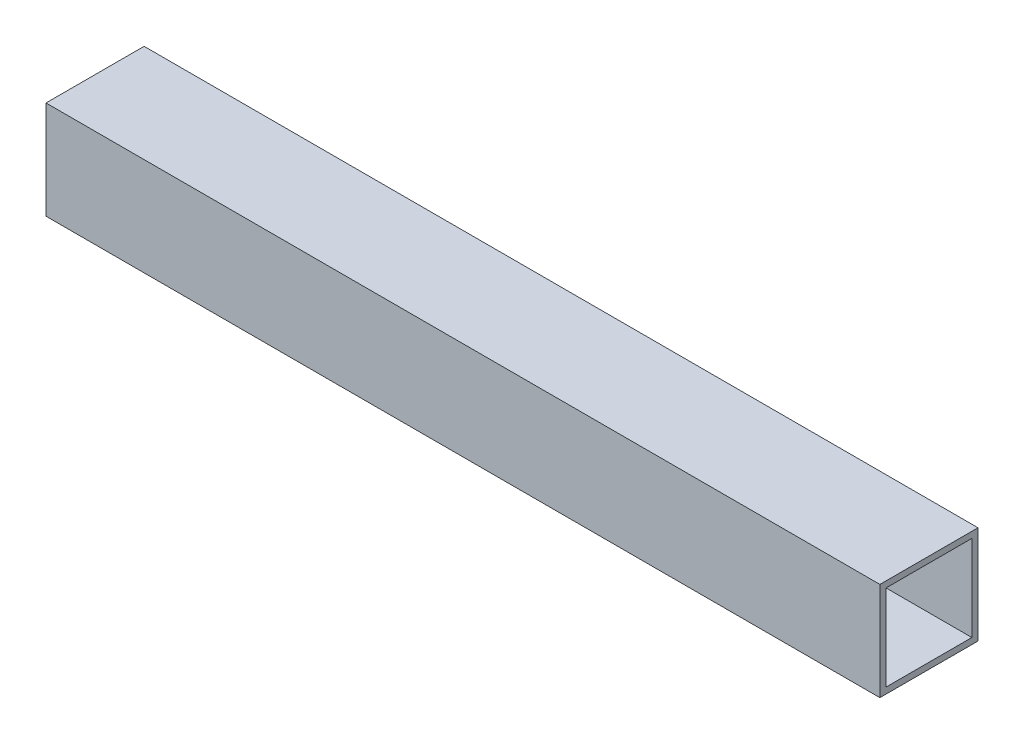
SolidWorks part; units mm, degrees
ref_plane "Front" through (0, 0, 0) normal (0, 0, 1) x (1, 0, 0)
ref_plane "Top" through (0, 0, 0) normal (0, 1, 0) x (1, 0, 0)
ref_plane "Right" through (0, 0, 0) normal (1, 0, 0) x (0, 0, -1)
sketch "Sketch1" plane through (0, 0, 0) normal (1, 0, 0) x (0, 0, -1)
  line L1 (-12.7, -12.7) -> (12.7, -12.7)
  line L2 (-12.7, -12.7) -> (-12.7, 12.7)
  line L3 (-12.7, 12.7) -> (12.7, 12.7)
  line L4 (12.7, -12.7) -> (12.7, 12.7)
  line L5 (-12.7, -12.7) -> (12.7, 12.7) construction
  line L6 (-12.7, 12.7) -> (12.7, -12.7) construction
  point P0 (0, 0)
  dimension "D1" = 25.4
extrude "Extrude-Thin1" add sketch "Sketch1" along normal blind 215.9 thin thin type one direction reverse wall 1.5875
